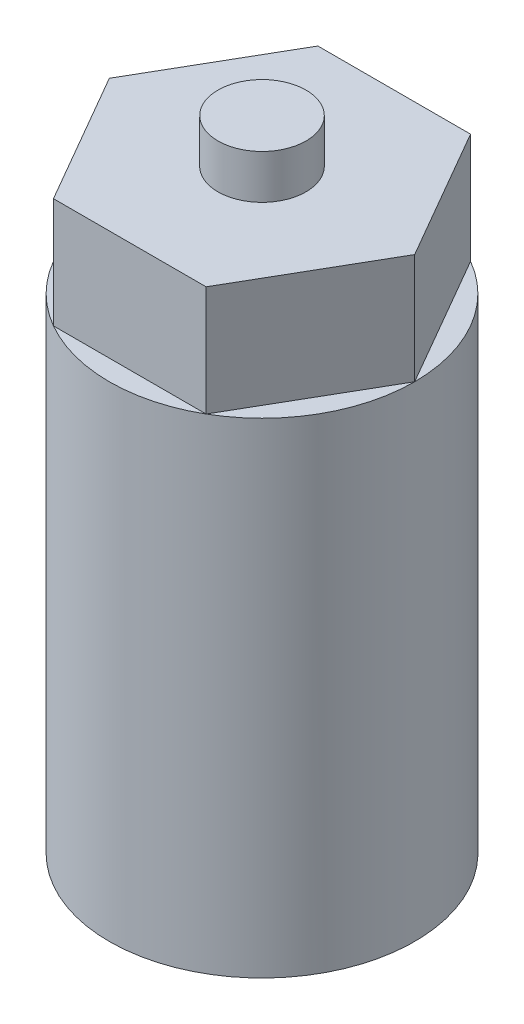
SolidWorks part; units mm, degrees
other "Markup1"
sketch "Sketch3" plane through (-6.9282, -22, -6.9282) normal (0, -1, 0) x (1, 0, 0)
ref_plane "Front Plane" through (0, 0, 0) normal (0, 0, 1) x (1, 0, 0)
ref_plane "Top Plane" through (0, 0, 0) normal (0, 1, 0) x (1, 0, 0)
ref_plane "Right Plane" through (0, 0, 0) normal (1, 0, 0) x (0, 0, -1)
sketch "Sketch1" plane through (0, 0, 0) normal (0, 1, 0) x (1, 0, 0)
  line L0 (-3.4641, -6) -> (3.4641, -6)
  line L1 (3.4641, -6) -> (6.9282, 0)
  line L2 (6.9282, 0) -> (3.4641, 6)
  line L3 (3.4641, 6) -> (-3.4641, 6)
  line L4 (-3.4641, 6) -> (-6.9282, 0)
  line L5 (-6.9282, 0) -> (-3.4641, -6)
  line L6 (-209.9765, -121.23) -> (43091.2937, 24878.77) construction
  line L7 (-199.7567, 115.3296) -> (43101.5135, -24884.6704) construction
  line L8 (0, -93.3064) -> (0, 49906.6936) construction
  circle A0 centre (0, 0) radius 2
  point P4 (0, 6)
  point P7 (0, -6)
  point P15 (5.1962, -3)
  point P16 (-5.1962, 3)
  dimension "D4" = 4
  dimension "D1" = 60
  dimension "D2" = 60
  dimension "D3" = 12
extrude "Boss-Extrude1" add sketch "Sketch1" along normal blind 5 contours A0 | L4 L5 L0 L1 L2 L3 A0 region at (-5.0374, 0, 2.9083) region at (0, 0, 0)
extrude "Boss-Extrude2" add sketch "Sketch1<3>" along normal blind 7 contours A0 region at (0, 0, 0)
sketch "Sketch1<3>" plane through (0, 0, 0) normal (0, 1, 0) x (1, 0, 0) same geometry as "Sketch1"
sketch "Sketch2" plane through (0, 0, 0) normal (0, -1, 0) x (1, 0, 0)
  line L0 (-1.7937, 2.65) -> (1.7937, 2.65)
  arc A2 (1.7937, 2.65) -> (-1.7937, 2.65) centre (0, 0) cw
  circle A3 centre (0, 0) radius 6.9282
  dimension "D1" = 3.2
  dimension "D2" = 2.65
extrude "Boss-Extrude3" add sketch "Sketch2" along normal blind 22
